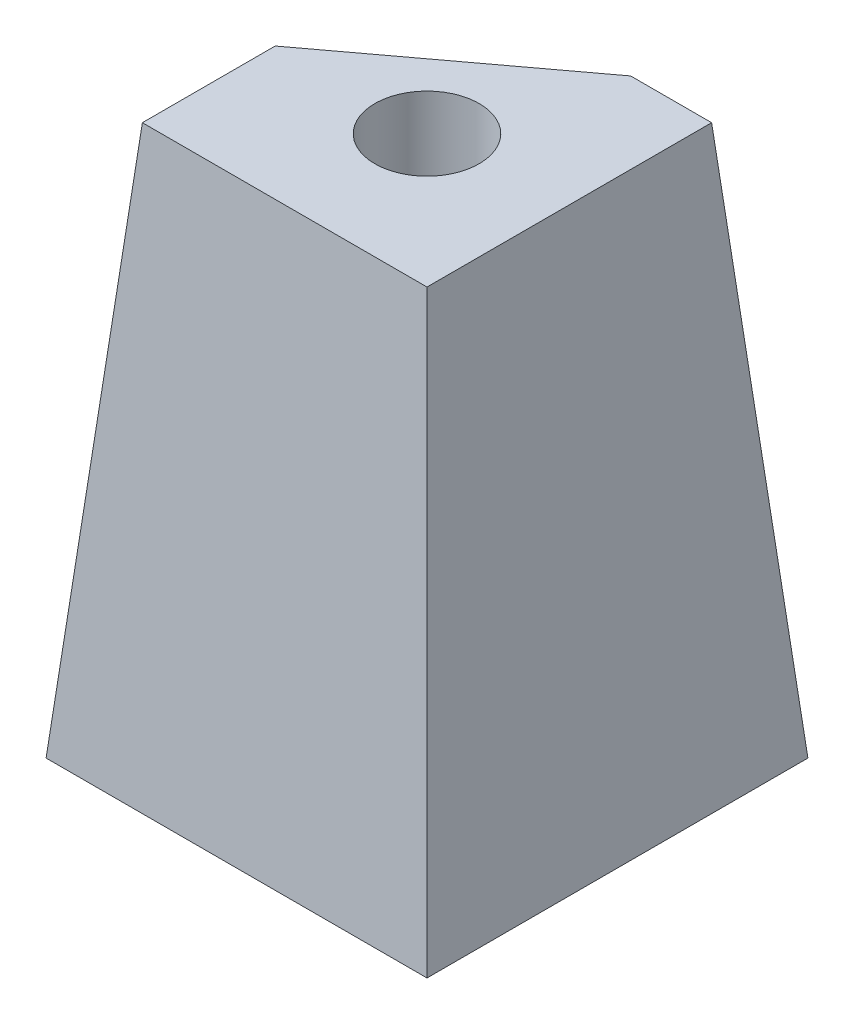
SolidWorks part; units mm, degrees
ref_plane "Front Plane" through (0, 0, 0) normal (0, 0, 1) x (1, 0, 0)
ref_plane "Top Plane" through (0, 0, 0) normal (0, 1, 0) x (1, 0, 0)
ref_plane "Right Plane" through (0, 0, 0) normal (1, 0, 0) x (0, 0, -1)
sketch "Sketch1" plane through (0, 0, 0) normal (0, 1, 0) x (1, 0, 0)
  line L0 (-4.5796, -0.2013) -> (6.1532, 7.7987)
  line L1 (6.1532, 7.7987) -> (10.4204, 7.7987)
  line L2 (10.4204, 7.7987) -> (10.4204, -7.2013)
  line L3 (10.4204, -7.2013) -> (-4.5796, -7.2013)
  line L4 (-4.5796, -7.2013) -> (-4.5796, -0.2013)
  dimension "D1" = 15
  dimension "D2" = 15
  dimension "D4" = 7
  dimension "D5" = 126.7
extrude "Boss-Extrude1" add sketch "Sketch1" along normal blind 29
sketch "Sketch2" plane through (0, 0, 0) normal (0, -1, 0) x (1, 0, 0)
  line L0 (-4.5796, 0.2013) -> (-4.5796, 7.2013) construction
  line L1 (10.4204, 7.2013) -> (10.4204, -7.7987) construction
  line L2 (-4.5796, 7.2013) -> (10.4204, 7.2013) construction
  circle A0 centre (-0.5796, 2.2013) radius 1.5
  circle A1 centre (7.4204, 2.2013) radius 2
  dimension "D1" = 3
  dimension "D3" = 4
  dimension "D2" = 4
  dimension "D4" = 3
  dimension "D5" = 5
  dimension "D6" = 5
extrude "Cut-Extrude1" cut sketch "Sketch2" against normal blind 10
sketch "Sketch3" plane through (0, 29, 0) normal (0, 1, 0) x (1, 0, 0)
  line L0 (10.4204, -7.2013) -> (10.4204, 7.7987) construction
  line L1 (-4.5796, -7.2013) -> (10.4204, -7.2013) construction
  circle A0 centre (3.4204, -0.2013) radius 2.75
  dimension "D1" = 5.5
  dimension "D2" = 7
  dimension "D3" = 7
extrude "Cut-Extrude2" cut sketch "Sketch3" against normal blind 6
draft "Draft1" type of draft neutral plane draft angle 5 faces to draft 5 face at (8.2868, 14.5, -7.7987) face at (10.4204, 14.5, -0.2987) face at (2.9204, 14.5, 7.2013) face at (-4.5796, 14.5, 3.7013) face at (0.7868, 14.5, -3.7987) neutral plane through (0, 29, 0) neutral plane normal (0, 1, 0) parameters "D1"=5
